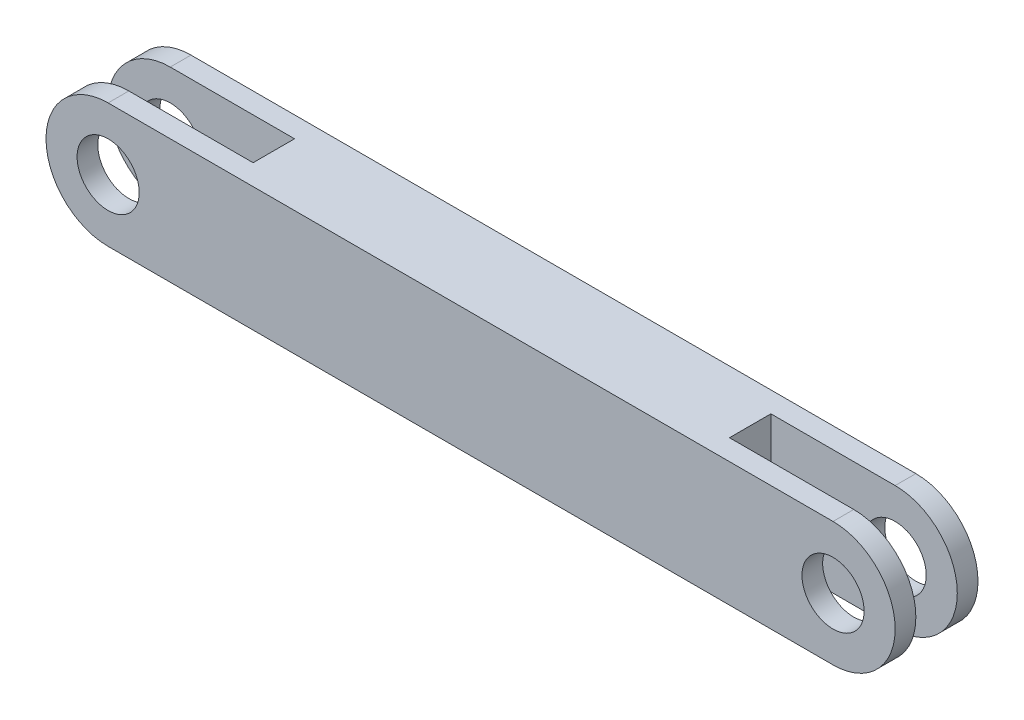
SolidWorks part; units mm, degrees
ref_plane "前视基准面" through (0, 0, 0) normal (0, 0, 1) x (1, 0, 0)
ref_plane "上视基准面" through (0, 0, 0) normal (0, 1, 0) x (1, 0, 0)
ref_plane "右视基准面" through (0, 0, 0) normal (1, 0, 0) x (0, 0, -1)
sketch "草图1" plane through (0, 0, 0) normal (0, 0, 1) x (1, 0, 0)
  line L0 (-35, 0) -> (35, 0) construction
  line L1 (-35, 6) -> (35, 6)
  line L2 (-35, -6) -> (35, -6)
  arc A0 (-35, 6) -> (-35, -6) centre (-35, 0) ccw
  arc A1 (35, -6) -> (35, 6) centre (35, 0) ccw
  circle A2 centre (-35, 0) radius 3
  circle A3 centre (35, 0) radius 3
  point P3 (0, 0)
  dimension "D3" = 6
  dimension "D4" = 6
  dimension "D1" = 12
  dimension "D2" = 70
extrude "凸台-拉伸1" add sketch "草图1" along normal blind 8
sketch "草图2" plane through (0, 6, 0) normal (0, 1, 0) x (1, 0, 0)
  line L0 (-35, 0) -> (-41, 0) construction
  line L1 (-41, -2) -> (-23, -2)
  line L2 (-41, -2) -> (-41, -6)
  line L3 (-41, -6) -> (-23, -6)
  line L4 (-23, -2) -> (-23, -6)
  line L5 (-35, -8) -> (-35, 0) construction
  line L6 (0, 0) -> (0, -26.8414) construction
  line L7 (23, -2) -> (23, -6)
  line L8 (41, -6) -> (23, -6)
  line L9 (41, -2) -> (41, -6)
  line L10 (41, -2) -> (23, -2)
  dimension "D1" = 4
  dimension "D2" = 2
  dimension "D3" = 6
  dimension "D4" = 18
extrude "切除-拉伸1" cut sketch "草图2" against normal through all
